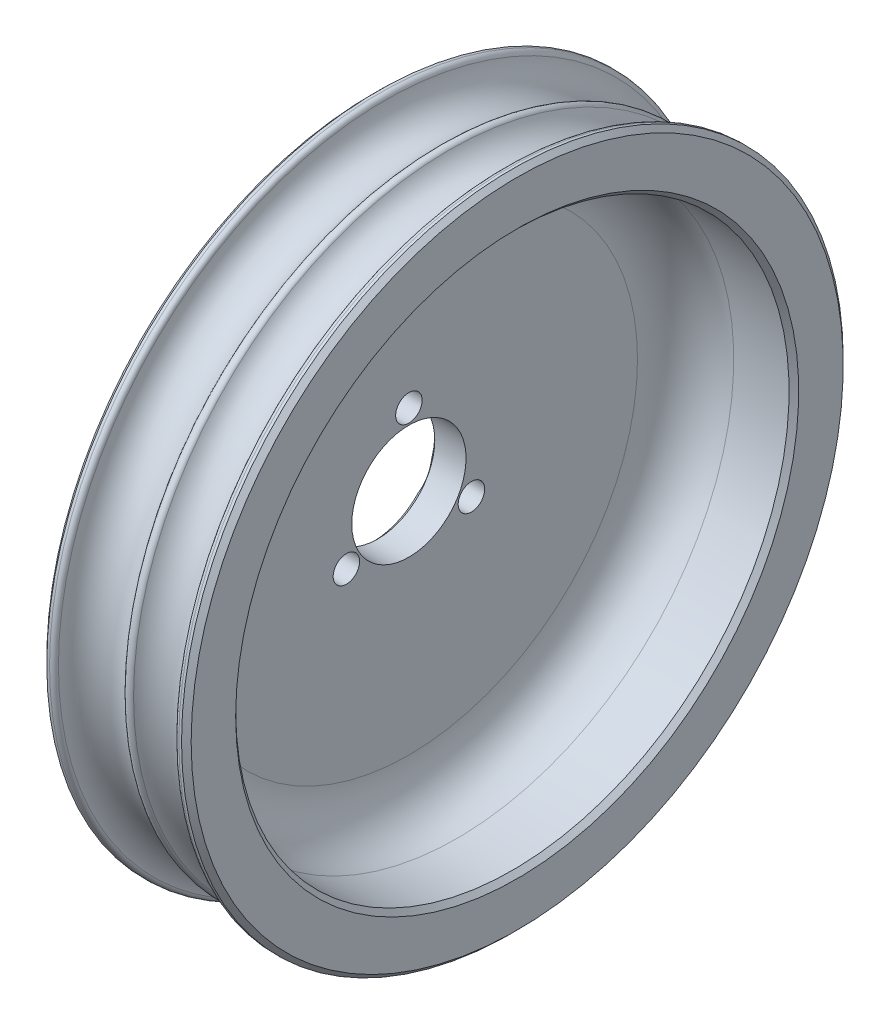
SolidWorks part; units mm, degrees
ref_plane "前视基准面" through (0, 0, 0) normal (0, 0, 1) x (1, 0, 0)
ref_plane "上视基准面" through (0, 0, 0) normal (0, 1, 0) x (1, 0, 0)
ref_plane "右视基准面" through (0, 0, 0) normal (1, 0, 0) x (0, 0, -1)
sketch "草图1" plane through (0, 0, 0) normal (0, 0, 1) x (1, 0, 0)
  line L0 (-16.5806, 0) -> (15.9821, 0) construction
  line L1 (0, 30.6673) -> (0, -24.0928) construction
  line L3 (6, 23) -> (0, 23)
  line L6 (5, 27.5) -> (6, 27.5)
  line L7 (6, 27.5) -> (6, 23)
  line L8 (-6, 23) -> (0, 23)
  line L9 (-6, 27.5) -> (-6, 23)
  line L10 (-5, 27.5) -> (-6, 27.5)
  arc A0 (0, 27.5) -> (5, 27.5) centre (2.5, 27.5) ccw
  arc A2 (0, 27.5) -> (-5, 27.5) centre (-2.5, 27.5) cw
  point P10 (3, 23)
  point P15 (-3, 23)
  dimension "D1" = 2.5
  dimension "D2" = 23
  dimension "D3" = 27.5
  dimension "D4" = 12
revolve "旋转1" add sketch "草图1" angle 360 about L0
fillet "圆角1" radius 0.4 3 edges at (-5, 0, 27.5) (5, 0, 27.5) (0, 0, 27.5)
sketch "草图4" plane through (-6, 0, 0) normal (-1, 0, 0) x (0, 0, 1)
  circle A0 centre (0, 0) radius 23 construction
  circle A1 centre (0, 0) radius 23
  circle A6 centre (0, 6) radius 1.1
  circle A7 centre (5.1962, -3) radius 1.1
  circle A8 centre (-5.1962, -3) radius 1.1
  circle A9 centre (0, 0) radius 4.75
  point P16 (0, 0)
  point P21 (0, 0)
  dimension "D1" = 9.5
  dimension "D2" = 2.2
  dimension "D4" = 2.2
  dimension "D3" = 2.2
extrude "凸台-拉伸1" add sketch "草图4" against normal blind 3
chamfer "倒角1" distance 0.4 angle 45 7 edges at (-6, 0, 4.75) (-6, 6, 1.1) (-6, -3, 6.2962) (-6, -3, -4.0962) (6, 0, 27.5) (6, 0, 23) (-6, 0, 27.5)
ref_plane "基准面1" through (2.5, 0, 0) normal (1, 0, 0) x (0, 0, -1)
sketch "草图2" plane through (2.5, 0, 0) normal (1, 0, 0) x (0, 0, -1)
  circle A0 centre (0, 0) radius 27.5 construction
  dimension "D1" = 55
ref_plane "基准面3" through (-2.5, 0, 0) normal (-1, 0, 0) x (0, 0, 1)
sketch "草图3" plane through (-2.5, 0, 0) normal (-1, 0, 0) x (0, 0, 1)
  circle A0 centre (0, 0) radius 27.5 construction
  dimension "D1" = 55
fillet "圆角2" radius 4 1 edges at (-3, 0, 23)
